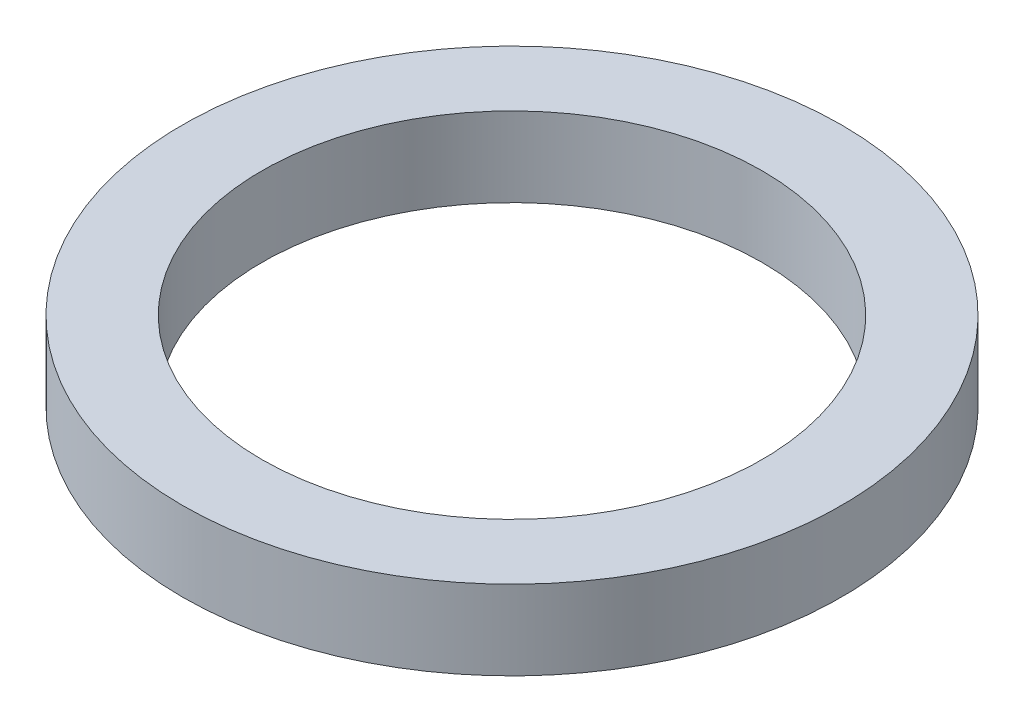
SolidWorks part; units mm, degrees
ref_plane "Front Plane" through (0, 0, 0) normal (0, 0, 1) x (1, 0, 0)
ref_plane "Top Plane" through (0, 0, 0) normal (0, 1, 0) x (1, 0, 0)
ref_plane "Right Plane" through (0, 0, 0) normal (1, 0, 0) x (0, 0, -1)
sketch "Sketch1" plane through (0, 0, 0) normal (0, 1, 0) x (1, 0, 0)
  circle A0 centre (0, 0) radius 4
  circle A1 centre (0, 0) radius 5.27
  dimension "8mm" = 8
  dimension "D2" = 1.27
extrude "Boss-Extrude1" add sketch "Sketch1" along normal blind 1.27
